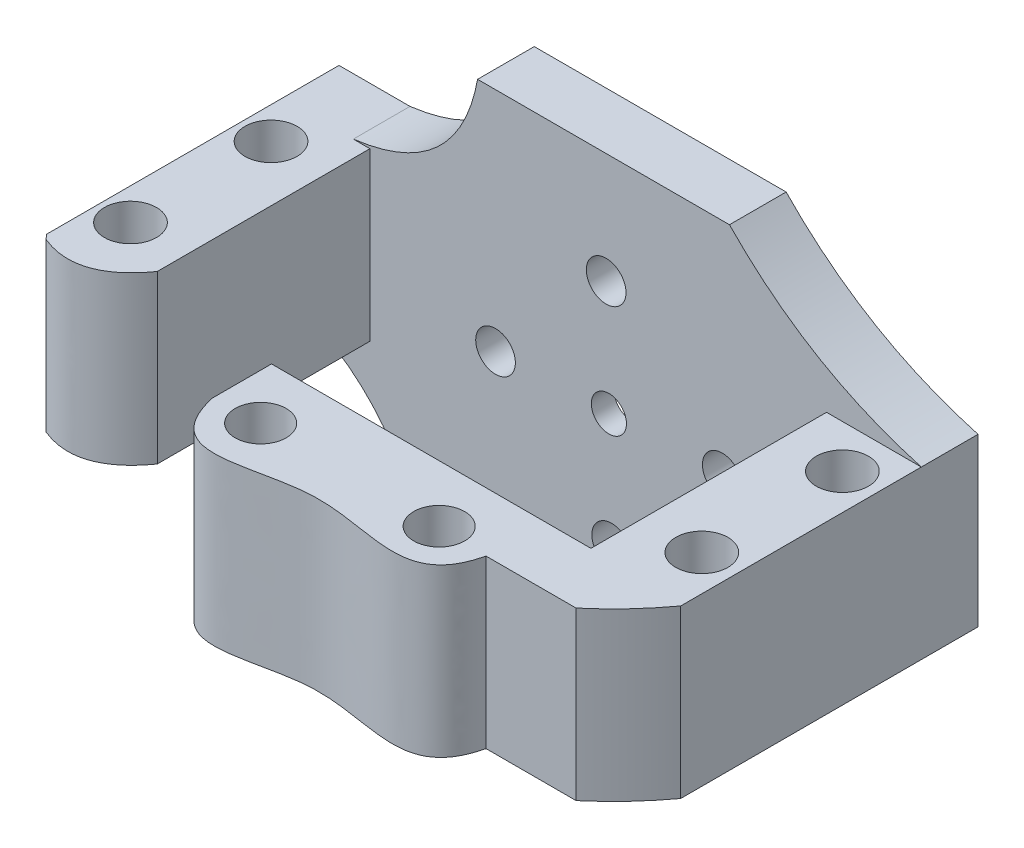
SolidWorks part; units mm, degrees
ref_plane "Front Plane" through (0, 0, 0) normal (0, 0, 1) x (1, 0, 0)
ref_plane "Top Plane" through (0, 0, 0) normal (0, 1, 0) x (1, 0, 0)
ref_plane "Right Plane" through (0, 0, 0) normal (1, 0, 0) x (0, 0, -1)
sketch "Sketch1" plane through (0, 0, 0) normal (0, 0, 1) x (1, 0, 0)
  line L201 (32.3843, -6.9757) -> (32.3843, 28.0894)
  line L202 (32.3843, 28.0894) -> (-24.3046, 28.0894)
  line L203 (-24.3046, 28.0894) -> (-24.3046, -6.9757)
  line L204 (-24.3046, -6.9757) -> (32.3843, -6.9757)
  line L1606 (1.9232, 7.8789) -> (2.0786, 7.8157)
  line L1607 (2.0505, 7.9883) -> (1.9232, 7.8789)
  line L1608 (1.8993, 8.0611) -> (2.0505, 7.9883)
  line L1609 (2.0332, 8.1623) -> (1.8993, 8.0611)
  line L1610 (1.887, 8.2445) -> (2.0332, 8.1623)
  line L1611 (2.0269, 8.337) -> (1.887, 8.2445)
  line L1612 (1.8861, 8.4282) -> (2.0269, 8.337)
  line L1613 (2.0316, 8.5118) -> (1.8861, 8.4282)
  line L1614 (1.8968, 8.6117) -> (2.0316, 8.5118)
  line L1615 (2.0473, 8.6859) -> (1.8968, 8.6117)
  line L1616 (1.919, 8.7941) -> (2.0473, 8.6859)
  line L1617 (2.0738, 8.8587) -> (1.919, 8.7941)
  line L1618 (1.9526, 8.9747) -> (2.0738, 8.8587)
  line L1619 (2.1112, 9.0295) -> (1.9526, 8.9747)
  line L1620 (1.9975, 9.1529) -> (2.1112, 9.0295)
  line L1621 (2.1592, 9.1976) -> (1.9975, 9.1529)
  line L1622 (2.0535, 9.3279) -> (2.1592, 9.1976)
  line L1623 (2.2177, 9.3624) -> (2.0535, 9.3279)
  line L1624 (2.1203, 9.4991) -> (2.2177, 9.3624)
  line L1625 (2.2864, 9.5232) -> (2.1203, 9.4991)
  line L1626 (2.1978, 9.6657) -> (2.2864, 9.5232)
  line L1627 (2.365, 9.6793) -> (2.1978, 9.6657)
  line L1628 (2.2856, 9.8271) -> (2.365, 9.6793)
  line L1629 (2.4533, 9.8302) -> (2.2856, 9.8271)
  line L1630 (2.3833, 9.9827) -> (2.4533, 9.8302)
  line L1631 (2.5509, 9.9753) -> (2.3833, 9.9827)
  line L1632 (2.4907, 10.1319) -> (2.5509, 9.9753)
  line L1633 (2.6575, 10.1139) -> (2.4907, 10.1319)
  line L1634 (2.6071, 10.274) -> (2.6575, 10.1139)
  line L1635 (2.7725, 10.2456) -> (2.6071, 10.274)
  line L1636 (2.7323, 10.4085) -> (2.7725, 10.2456)
  line L1637 (2.8956, 10.3698) -> (2.7323, 10.4085)
  line L1638 (2.8657, 10.5349) -> (2.8956, 10.3698)
  line L1639 (3.0262, 10.486) -> (2.8657, 10.5349)
  line L1640 (3.0067, 10.6527) -> (3.0262, 10.486)
  line L1641 (3.1638, 10.5938) -> (3.0067, 10.6527)
  line L1642 (3.1549, 10.7614) -> (3.1638, 10.5938)
  line L1643 (3.308, 10.6928) -> (3.1549, 10.7614)
  line L1644 (3.3096, 10.8605) -> (3.308, 10.6928)
  line L1645 (3.4581, 10.7825) -> (3.3096, 10.8605)
  line L1646 (3.4702, 10.9498) -> (3.4581, 10.7825)
  line L1647 (3.6135, 10.8625) -> (3.4702, 10.9498)
  line L1648 (3.6361, 11.0288) -> (3.6135, 10.8625)
  line L1649 (3.7736, 10.9327) -> (3.6361, 11.0288)
  line L1650 (3.8066, 11.0972) -> (3.7736, 10.9327)
  line L1651 (3.9379, 10.9927) -> (3.8066, 11.0972)
  line L1652 (3.9811, 11.1548) -> (3.9379, 10.9927)
  line L1653 (4.1055, 11.0422) -> (3.9811, 11.1548)
  line L1654 (4.1589, 11.2013) -> (4.1055, 11.0422)
  line L1655 (4.276, 11.0812) -> (4.1589, 11.2013)
  line L1656 (4.3392, 11.2366) -> (4.276, 11.0812)
  line L1657 (4.4486, 11.1093) -> (4.3392, 11.2366)
  line L1658 (4.5214, 11.2604) -> (4.4486, 11.1093)
  line L1659 (4.6225, 11.1266) -> (4.5214, 11.2604)
  line L1660 (4.7047, 11.2728) -> (4.6225, 11.1266)
  line L1661 (4.7973, 11.1329) -> (4.7047, 11.2728)
  line L1662 (4.8885, 11.2737) -> (4.7973, 11.1329)
  line L1663 (4.972, 11.1282) -> (4.8885, 11.2737)
  line L1664 (5.0719, 11.263) -> (4.972, 11.1282)
  line L1665 (5.1462, 11.1125) -> (5.0719, 11.263)
  line L1666 (5.2543, 11.2408) -> (5.1462, 11.1125)
  line L1667 (5.319, 11.086) -> (5.2543, 11.2408)
  line L1668 (5.435, 11.2072) -> (5.319, 11.086)
  line L1669 (5.4898, 11.0486) -> (5.435, 11.2072)
  line L1670 (5.6132, 11.1623) -> (5.4898, 11.0486)
  line L1671 (5.6579, 11.0006) -> (5.6132, 11.1623)
  line L1672 (5.7882, 11.1063) -> (5.6579, 11.0006)
  line L1673 (5.8227, 10.9421) -> (5.7882, 11.1063)
  line L1674 (5.9594, 11.0394) -> (5.8227, 10.9421)
  line L1675 (5.9835, 10.8734) -> (5.9594, 11.0394)
  line L1676 (6.126, 10.962) -> (5.9835, 10.8734)
  line L1677 (6.1396, 10.7948) -> (6.126, 10.962)
  line L1678 (6.2874, 10.8742) -> (6.1396, 10.7948)
  line L1679 (6.2905, 10.7064) -> (6.2874, 10.8742)
  line L1680 (6.443, 10.7764) -> (6.2905, 10.7064)
  line L1681 (6.4356, 10.6088) -> (6.443, 10.7764)
  line L1682 (6.5921, 10.6691) -> (6.4356, 10.6088)
  line L1683 (6.5742, 10.5023) -> (6.5921, 10.6691)
  line L1684 (6.7343, 10.5526) -> (6.5742, 10.5023)
  line L1685 (6.7059, 10.3873) -> (6.7343, 10.5526)
  line L1686 (6.8688, 10.4275) -> (6.7059, 10.3873)
  line L1687 (6.8301, 10.2642) -> (6.8688, 10.4275)
  line L1688 (6.9952, 10.2941) -> (6.8301, 10.2642)
  line L1689 (6.9463, 10.1336) -> (6.9952, 10.2941)
  line L1690 (7.113, 10.1531) -> (6.9463, 10.1336)
  line L1691 (7.0541, 9.9959) -> (7.113, 10.1531)
  line L1692 (7.2216, 10.0049) -> (7.0541, 9.9959)
  line L1693 (7.153, 9.8518) -> (7.2216, 10.0049)
  line L1694 (7.3208, 9.8502) -> (7.153, 9.8518)
  line L1695 (7.2427, 9.7017) -> (7.3208, 9.8502)
  line L1696 (7.4101, 9.6896) -> (7.2427, 9.7017)
  line L1697 (7.3228, 9.5463) -> (7.4101, 9.6896)
  line L1698 (7.4891, 9.5237) -> (7.3228, 9.5463)
  line L1699 (7.393, 9.3861) -> (7.4891, 9.5237)
  line L1700 (7.5575, 9.3531) -> (7.393, 9.3861)
  line L1701 (7.453, 9.2219) -> (7.5575, 9.3531)
  line L1702 (7.6151, 9.1787) -> (7.453, 9.2219)
  line L1703 (7.5025, 9.0542) -> (7.6151, 9.1787)
  line L1704 (7.6616, 9.0009) -> (7.5025, 9.0542)
  line L1705 (7.5414, 8.8838) -> (7.6616, 9.0009)
  line L1706 (7.6969, 8.8206) -> (7.5414, 8.8838)
  line L1707 (7.5696, 8.7112) -> (7.6969, 8.8206)
  line L1708 (7.7207, 8.6384) -> (7.5696, 8.7112)
  line L1709 (7.5868, 8.5372) -> (7.7207, 8.6384)
  line L1710 (7.7331, 8.455) -> (7.5868, 8.5372)
  line L1711 (7.5931, 8.3625) -> (7.7331, 8.455)
  line L1712 (7.7339, 8.2713) -> (7.5931, 8.3625)
  line L1713 (7.5884, 8.1877) -> (7.7339, 8.2713)
  line L1714 (7.7232, 8.0878) -> (7.5884, 8.1877)
  line L1715 (7.5728, 8.0136) -> (7.7232, 8.0878)
  line L1716 (7.701, 7.9054) -> (7.5728, 8.0136)
  line L1717 (7.5462, 7.8408) -> (7.701, 7.9054)
  line L1718 (7.6674, 7.7248) -> (7.5462, 7.8408)
  line L1719 (7.5089, 7.67) -> (7.6674, 7.7248)
  line L1720 (7.6226, 7.5466) -> (7.5089, 7.67)
  line L1721 (7.4609, 7.5019) -> (7.6226, 7.5466)
  line L1722 (7.5666, 7.3716) -> (7.4609, 7.5019)
  line L1723 (7.4024, 7.3371) -> (7.5666, 7.3716)
  line L1724 (7.4997, 7.2004) -> (7.4024, 7.3371)
  line L1725 (7.3337, 7.1763) -> (7.4997, 7.2004)
  line L1726 (7.4222, 7.0338) -> (7.3337, 7.1763)
  line L1727 (7.255, 7.0202) -> (7.4222, 7.0338)
  line L1728 (7.3345, 6.8724) -> (7.255, 7.0202)
  line L1729 (7.1667, 6.8693) -> (7.3345, 6.8724)
  line L1730 (7.2367, 6.7168) -> (7.1667, 6.8693)
  line L1731 (7.0691, 6.7242) -> (7.2367, 6.7168)
  line L1732 (7.1294, 6.5676) -> (7.0691, 6.7242)
  line L1733 (6.9626, 6.5856) -> (7.1294, 6.5676)
  line L1734 (7.0129, 6.4255) -> (6.9626, 6.5856)
  line L1735 (6.8476, 6.4539) -> (7.0129, 6.4255)
  line L1736 (6.8877, 6.291) -> (6.8476, 6.4539)
  line L1737 (6.7245, 6.3297) -> (6.8877, 6.291)
  line L1738 (6.7544, 6.1646) -> (6.7245, 6.3297)
  line L1739 (6.5939, 6.2135) -> (6.7544, 6.1646)
  line L1740 (6.6133, 6.0468) -> (6.5939, 6.2135)
  line L1741 (6.4562, 6.1057) -> (6.6133, 6.0468)
  line L1742 (6.4652, 5.9381) -> (6.4562, 6.1057)
  line L1743 (6.3121, 6.0067) -> (6.4652, 5.9381)
  line L1744 (6.3105, 5.839) -> (6.3121, 6.0067)
  line L1745 (6.162, 5.917) -> (6.3105, 5.839)
  line L1746 (6.1499, 5.7497) -> (6.162, 5.917)
  line L1747 (6.0066, 5.8369) -> (6.1499, 5.7497)
  line L1748 (5.984, 5.6707) -> (6.0066, 5.8369)
  line L1749 (5.8464, 5.7668) -> (5.984, 5.6707)
  line L1750 (5.8134, 5.6023) -> (5.8464, 5.7668)
  line L1751 (5.6822, 5.7068) -> (5.8134, 5.6023)
  line L1752 (5.6389, 5.5447) -> (5.6822, 5.7068)
  line L1753 (5.5145, 5.6572) -> (5.6389, 5.5447)
  line L1754 (5.4612, 5.4982) -> (5.5145, 5.6572)
  line L1755 (5.3441, 5.6183) -> (5.4612, 5.4982)
  line L1756 (5.2808, 5.4629) -> (5.3441, 5.6183)
  line L1757 (5.1715, 5.5902) -> (5.2808, 5.4629)
  line L1758 (5.0986, 5.4391) -> (5.1715, 5.5902)
  line L1759 (4.9975, 5.5729) -> (5.0986, 5.4391)
  line L1760 (4.9153, 5.4267) -> (4.9975, 5.5729)
  line L1761 (4.8228, 5.5666) -> (4.9153, 5.4267)
  line L1762 (4.7316, 5.4258) -> (4.8228, 5.5666)
  line L1763 (4.648, 5.5713) -> (4.7316, 5.4258)
  line L1764 (4.5481, 5.4365) -> (4.648, 5.5713)
  line L1765 (4.4739, 5.587) -> (4.5481, 5.4365)
  line L1766 (4.3657, 5.4587) -> (4.4739, 5.587)
  line L1767 (4.3011, 5.6135) -> (4.3657, 5.4587)
  line L1768 (4.1851, 5.4923) -> (4.3011, 5.6135)
  line L1769 (4.1302, 5.6509) -> (4.1851, 5.4923)
  line L1770 (4.0069, 5.5372) -> (4.1302, 5.6509)
  line L1771 (3.9621, 5.6989) -> (4.0069, 5.5372)
  line L1772 (3.8319, 5.5932) -> (3.9621, 5.6989)
  line L1773 (3.7974, 5.7574) -> (3.8319, 5.5932)
  line L1774 (3.6607, 5.6601) -> (3.7974, 5.7574)
  line L1775 (3.6366, 5.8261) -> (3.6607, 5.6601)
  line L1776 (3.4941, 5.7375) -> (3.6366, 5.8261)
  line L1777 (3.4804, 5.9047) -> (3.4941, 5.7375)
  line L1778 (3.3327, 5.8253) -> (3.4804, 5.9047)
  line L1779 (3.3295, 5.9931) -> (3.3327, 5.8253)
  line L1780 (3.1771, 5.9231) -> (3.3295, 5.9931)
  line L1781 (3.1845, 6.0907) -> (3.1771, 5.9231)
  line L1782 (3.0279, 6.0304) -> (3.1845, 6.0907)
  line L1783 (3.0458, 6.1972) -> (3.0279, 6.0304)
  line L1784 (2.8858, 6.1469) -> (3.0458, 6.1972)
  line L1785 (2.9142, 6.3122) -> (2.8858, 6.1469)
  line L1786 (2.7513, 6.272) -> (2.9142, 6.3122)
  line L1787 (2.79, 6.4353) -> (2.7513, 6.272)
  line L1788 (2.6249, 6.4054) -> (2.79, 6.4353)
  line L1789 (2.6737, 6.5659) -> (2.6249, 6.4054)
  line L1790 (2.5071, 6.5464) -> (2.6737, 6.5659)
  line L1791 (2.5659, 6.7036) -> (2.5071, 6.5464)
  line L1792 (2.3984, 6.6946) -> (2.5659, 6.7036)
  line L1793 (2.467, 6.8477) -> (2.3984, 6.6946)
  line L1794 (2.2992, 6.8493) -> (2.467, 6.8477)
  line L1795 (2.3773, 6.9978) -> (2.2992, 6.8493)
  line L1796 (2.21, 7.0099) -> (2.3773, 6.9978)
  line L1797 (2.2972, 7.1532) -> (2.21, 7.0099)
  line L1798 (2.131, 7.1758) -> (2.2972, 7.1532)
  line L1799 (2.2271, 7.3134) -> (2.131, 7.1758)
  line L1800 (2.0626, 7.3463) -> (2.2271, 7.3134)
  line L1801 (2.1671, 7.4776) -> (2.0626, 7.3463)
  line L1802 (2.005, 7.5208) -> (2.1671, 7.4776)
  line L1803 (2.1175, 7.6453) -> (2.005, 7.5208)
  line L1804 (1.9585, 7.6986) -> (2.1175, 7.6453)
  line L1805 (2.0786, 7.8157) -> (1.9585, 7.6986)
  dimension "D1" = 56.6889
  dimension "D2" = 35.0651
extrude "Boss-Extrude1" add sketch "Sketch1" against normal blind 3 and the other way blind 2
sketch "Sketch22" plane through (0, 0, -3) normal (0, 0, -1) x (-1, 0, 0)
  circle A0 centre (-4.8204, 8.3365) radius 14.8896
  point P2 (0, 0)
sketch "Sketch2" plane through (0, 0, 2) normal (0, 0, 1) x (1, 0, 0)
  line L1 (-16.2597, 18.0397) -> (-16.2597, 3.3287)
  line L2 (-18.9031, 18.0397) -> (-16.2597, 18.0397)
  line L3 (-16.2597, 3.3287) -> (-25.5352, 3.3287)
  line L4 (-25.5352, 3.3287) -> (-25.5352, 18.0397)
  line L5 (-25.5352, 18.0397) -> (-18.9031, 18.0397)
  line L6 (32.3843, 28.0894) -> (-24.3046, 28.0894) construction
  line L15 (33.0179, 18.0397) -> (24.0179, 18.0397)
  line L16 (33.0179, 18.0397) -> (33.0179, 3.3287)
  line L17 (33.0179, 3.3287) -> (24.0179, 3.3287)
  line L18 (24.0179, 18.0397) -> (24.0179, 3.3287)
  dimension "D1" = 14.711
  dimension "D2" = 9
  dimension "D3" = 9.2755
  dimension "D4" = 14.711
  dimension "D6" = 10.0498
extrude "Boss-Extrude2" add sketch "Sketch2" along normal blind 26 and the other way blind 5
sketch "Sketch5" plane through (0, 0, 2) normal (0, 0, 1) x (1, 0, 0)
  circle A0 centre (5.4928, 7.4278) radius 5.0977
extrude "Boss-Extrude4" add sketch "Sketch5" against normal blind 2
sketch "Sketch6" plane through (0, 0, -3) normal (0, 0, -1) x (-1, 0, 0)
  circle A2 centre (-4.8204, 8.3365) radius 1.55
extrude "Cut-Extrude2" cut sketch "Sketch6" against normal blind 12
sketch "Sketch9" plane through (0, 3.3287, 0) normal (0, -1, 0) x (1, 0, 0)
  circle A0 centre (-21.1821, 18.2) radius 2.3
  circle A1 centre (-21.1821, 5.8) radius 2.3
  circle A2 centre (29.2179, 5.8) radius 2.3
  circle A3 centre (29.2179, 18.2) radius 2.3
extrude "Cut-Extrude3" cut sketch "Sketch9" against normal through all
sketch "Sketch13" plane through (0, 0, 28) normal (0, 0, 1) x (1, 0, 0)
  line L0 (-16.2597, 18.0397) -> (-25.5352, 18.0397) construction
  line L1 (-25.3316, 35.5979) -> (-17.7227, 35.5979)
  line L2 (-25.3316, 35.5979) -> (-25.3316, 18.0397)
  line L3 (-25.3316, 18.0397) -> (-17.7227, 18.0397)
  line L4 (-17.7227, 35.5979) -> (-17.7227, 18.0397)
extrude "Cut-Extrude4" cut sketch "Sketch13" against normal through all
sketch "Sketch16" plane through (0, 3.3287, 0) normal (0, -1, 0) x (1, 0, 0)
  line L0 (-26.3544, 19.3799) -> (-27.7873, 28.4979)
  line L1 (-27.7873, 28.4979) -> (-17.8498, 28)
  line L2 (34.734, 19.3799) -> (34.734, 30.0661)
  line L3 (34.734, 30.0661) -> (27.926, 28)
  line L4 (24.0179, 28) -> (33.0179, 28) construction
  line L5 (-25.5352, 28) -> (-16.2597, 28) construction
  spline S0 degree 2 poles (-17.8498, 28) (-23.2521, 24.7636) (-26.3544, 19.3799) knots 0 0 0 1 1 1
  spline S1 degree 2 poles (27.926, 28) (32.2086, 24.36) (34.734, 19.3799) knots 0 0 0 1 1 1
extrude "Cut-Extrude6" cut sketch "Sketch16" against normal through all
sketch "Sketch17" plane through (0, 18.0397, 0) normal (0, 1, 0) x (1, 0, 0)
  line L1 (32.3797, 4.6933) -> (39.5419, 4.6933)
  line L2 (32.3797, 4.6933) -> (32.3797, -27.9347)
  line L3 (32.3797, -27.9347) -> (39.5419, -27.9347)
  line L4 (39.5419, 4.6933) -> (39.5419, -27.9347)
  line L5 (-31.1449, 5.7148) -> (-23.9872, 5.7148)
  line L6 (-31.1449, 5.7148) -> (-31.1449, -25.337)
  line L7 (-31.1449, -25.337) -> (-23.9872, -25.337)
  line L8 (-23.9872, 5.7148) -> (-23.9872, -25.337)
extrude "Cut-Extrude7" cut sketch "Sketch17" against normal through all and the other way blind 10
ref_axis "Axis1" through (4.8204, 8.3365, -3) along (0, 0, -1)
sketch "Sketch23" plane through (0, 0, -3) normal (0, 0, -1) x (-1, 0, 0)
  line L1 (-4.8204, -984.6635) -> (-4.8204, 15.3365) construction
  arc A0 (0.9241, 12.3365) -> (-0.8204, 14.081) centre (-4.8204, 8.3365) ccw
  arc A1 (-8.8204, 14.081) -> (-10.565, 12.3365) centre (-4.8204, 8.3365) ccw
  arc A2 (-10.565, 4.3365) -> (-8.8204, 2.5919) centre (-4.8204, 8.3365) ccw
  arc A3 (-0.8204, 2.5919) -> (0.9241, 4.3365) centre (-4.8204, 8.3365) ccw
  spline S0 degree 3 poles (-4.8204, 26.3365) (-1.2764, 26.7096) (-1.4325, 20.6709) (-0.5027, 16.5348) (-0.8204, 14.081) knots 0 0 0 0 0.519506 1 1 1 1
  spline S1 degree 3 poles (-4.8204, 26.3365) (-8.3644, 26.7096) (-8.2084, 20.6709) (-9.1382, 16.5348) (-8.8204, 14.081) knots 0 0 0 0 0.519506 1 1 1 1
  spline S2 degree 3 poles (13.1796, 8.3365) (13.5527, 11.8805) (7.514, 11.7244) (3.3779, 12.6542) (0.9241, 12.3365) knots 0 0 0 0 0.519506 1 1 1 1
  spline S3 degree 3 poles (13.1796, 8.3365) (13.5527, 4.7925) (7.514, 4.9485) (3.3779, 4.0187) (0.9241, 4.3365) knots 0 0 0 0 0.519506 1 1 1 1
  spline S4 degree 3 poles (-4.8204, -9.6635) (-1.2764, -10.0367) (-1.4325, -3.998) (-0.5027, 0.1381) (-0.8204, 2.5919) knots 0 0 0 0 0.519506 1 1 1 1
  spline S5 degree 3 poles (-4.8204, -9.6635) (-8.3644, -10.0367) (-8.2084, -3.998) (-9.1382, 0.1381) (-8.8204, 2.5919) knots 0 0 0 0 0.519506 1 1 1 1
  spline S6 degree 3 poles (-22.8204, 8.3365) (-23.1936, 4.7925) (-17.1549, 4.9485) (-13.0188, 4.0187) (-10.565, 4.3365) knots 0 0 0 0 0.519506 1 1 1 1
  spline S7 degree 3 poles (-22.8204, 8.3365) (-23.1936, 11.8805) (-17.1549, 11.7244) (-13.0188, 12.6542) (-10.565, 12.3365) knots 0 0 0 0 0.519506 1 1 1 1
  point P5 (0, 0)
  point P45 (-4.8204, 8.3365)
  dimension "D1" = 14
  dimension "D2" = 4
  dimension "D3" = 18
extrude "Cut-Extrude9" cut sketch "Sketch23" against normal blind 2.5
sketch "Sketch24" plane through (0, 0, -0.5) normal (0, 0, -1) x (-1, 0, 0)
  line L0 (-8.7502, 8.3365) -> (-1.444, 8.2095) construction
  circle A0 centre (5.1796, 8.0943) radius 1.75
  circle A1 centre (-5.0625, -1.6635) radius 1.75
  circle A2 centre (-14.8204, 8.5786) radius 1.75
  circle A3 centre (-4.5783, 18.3365) radius 1.75
  point P14 (-4.8204, 8.3365)
  dimension "D1" = 3.5
  dimension "D2" = 10
  dimension "D3" = 4
extrude "Cut-Extrude10" cut sketch "Sketch24" against normal through all
sketch "Sketch27" plane through (0, 0, -3) normal (0, 0, -1) x (-1, 0, 0)
  line L0 (-32.3843, 28.0894) -> (17.7227, 28.0894) construction
  line L3 (-8.226, -6.9757) -> (-32.3797, -6.9757) construction
  line L4 (17.7227, 18.0397) -> (23.9872, 20.8601)
  line L5 (17.8498, 3.3287) -> (23.9872, 3.3287) construction
  line L6 (17.8498, 3.3287) -> (23.9872, 3.3287)
  line L8 (23.9872, -6.9757) -> (-1.4148, -6.9757) construction
  line L9 (-16.9857, -6.9757) -> (-39.5902, -14.3879)
  line L10 (23.9872, 3.3287) -> (28.5026, -2.8105)
  line L11 (28.5026, -2.8105) -> (26.2449, -17.6245)
  line L12 (26.2449, -17.6245) -> (12.5289, -6.9757)
  line L13 (-39.5902, -14.3879) -> (-32.3797, 3.3287)
  line L14 (-15.4563, 28.0894) -> (-32.3797, 34.4787)
  line L15 (-32.3797, 34.4787) -> (-36.2714, 18.0397)
  line L16 (-36.2714, 18.0397) -> (-32.3797, 18.0397)
  line L17 (23.9872, 20.8601) -> (17.7227, 34.4787)
  line L18 (17.7227, 34.4787) -> (6.7625, 28.0894)
  spline S0 degree 2 poles (17.7227, 18.0397) (8.3953, 19.2274) (6.7625, 28.0894) knots 0 0 0 1 1 1
  spline S1 degree 2 poles (-32.3797, 3.3287) (-22.3298, 1.1088) (-16.9857, -6.9757) knots 0 0 0 1 1 1
  spline S2 degree 2 poles (-32.3797, 18.0397) (-22.4978, 20.8062) (-15.4563, 28.0894) knots 0 0 0 1 1 1
  spline S3 degree 2 poles (23.9872, 3.3287) (15.9883, 1.0749) (12.5289, -6.9757) knots 0 0 0 1 1 1
  line M8 (-1.4148, -6.9757) -> (23.9872, -6.9757)
  line M9 (23.9872, -6.9757) -> (23.9872, 18.0397)
  line M11 (17.7227, 18.0397) -> (17.7227, 28.0894)
  line M12 (17.7227, 28.0894) -> (-32.3843, 28.0894)
  line M13 (-32.3843, 28.0894) -> (-32.3843, 28.0397)
  line M14 (-32.3843, 28.0397) -> (-32.3797, 28.0397)
  line M15 (-32.3797, 28.0397) -> (-32.3797, -6.9757)
  line M16 (-32.3797, -6.9757) -> (-8.226, -6.9757)
extrude "Cut-Extrude12" cut sketch "Sketch27" against normal blind 10 contours S3 M9 M8 | S1 M15 M16 | S2 M15 M12 M13 M14 | S0 M11 M12 region at (26.5629, -3.0208, -3) region at (26.2088, 24.3766, -3) region at (-13.2172, 23.9379, -3) region at (-19.5953, -2.9846, -3)
sketch "Sketch28" plane through (24.0179, 0, 0) normal (-1, 0, 0) x (0, 0, 1)
  line L0 (22.7827, 18.0397) -> (22.7827, 3.3287)
  line L4 (28, 18.0397) -> (2, 18.0397)
  line L5 (2, 18.0397) -> (2, 3.3287)
  line L6 (2, 3.3287) -> (28, 3.3287)
  line L7 (28, 3.3287) -> (28, 18.0397)
  line L8 (28, 18.0397) -> (22.7827, 18.0397)
  line L9 (2, 18.0397) -> (2, 3.3287)
  line L10 (22.7827, 3.3287) -> (28, 3.3287)
  line L11 (28, 3.3287) -> (28, 18.0397)
  line M6 (28, 18.0397) -> (2, 18.0397)
  line M8 (2, 3.3287) -> (28, 3.3287)
  line M9 (28, 3.3287) -> (28, 18.0397)
  dimension "D1" = 0
extrude "Boss-Extrude5" add sketch "Sketch28" along normal up to surface (40.2776 mm away) contours L0 M6 M8 M9 region at (24.0179, 10.6842, 25.3913) up to face at (-16.2597, 10.6842, 15)
sketch "Sketch29" plane through (0, 3.3287, 0) normal (0, -1, 0) x (1, 0, 0)
  line L0 (-17.8498, 28) -> (27.926, 28) construction
  line L1 (-4.1561, 28) -> (19.986, 28)
  spline S0 degree 3 poles (-4.1561, 28) (-2.5916, 34.8688) (7.6216, 27.5746) (18.5398, 34.1335) (19.986, 28) knots 0 0 0 0 0.506239 1 1 1 1
extrude "Boss-Extrude6" add sketch "Sketch29" against normal up to surface (14.711 mm away) up to face at (26.9179, 18.0397, 18.2)
sketch "Sketch30" plane through (0, 3.3287, 0) normal (0, -1, 0) x (1, 0, 0)
  circle A0 centre (-0.1102, 27.7868) radius 2.25
  circle A1 centre (15.6384, 27.7868) radius 2.25
extrude "Cut-Extrude13" cut sketch "Sketch30" against normal through all
sketch "Sketch31" plane through (0, 3.3287, 0) normal (0, -1, 0) x (1, 0, 0)
  line L0 (-16.2597, 2) -> (-16.2597, 22.7827) construction
  line L1 (-4.1561, 28) -> (-4.1561, 22.7827)
  line L2 (-16.2597, 22.7827) -> (24.0179, 22.7827) construction
  line L3 (-4.1561, 22.7827) -> (-16.2597, 20.7577)
  line L4 (-24.8538, 22.5979) -> (-14.7388, 32.901)
  line L5 (-14.7388, 32.901) -> (-4.1561, 28)
  spline S0 degree 2 poles (-24.8538, 22.5979) (-19.7208, 25.596) (-16.2597, 20.7577) knots 0 0 0 1 1 1
extrude "Cut-Extrude14" cut sketch "Sketch31" against normal through all
